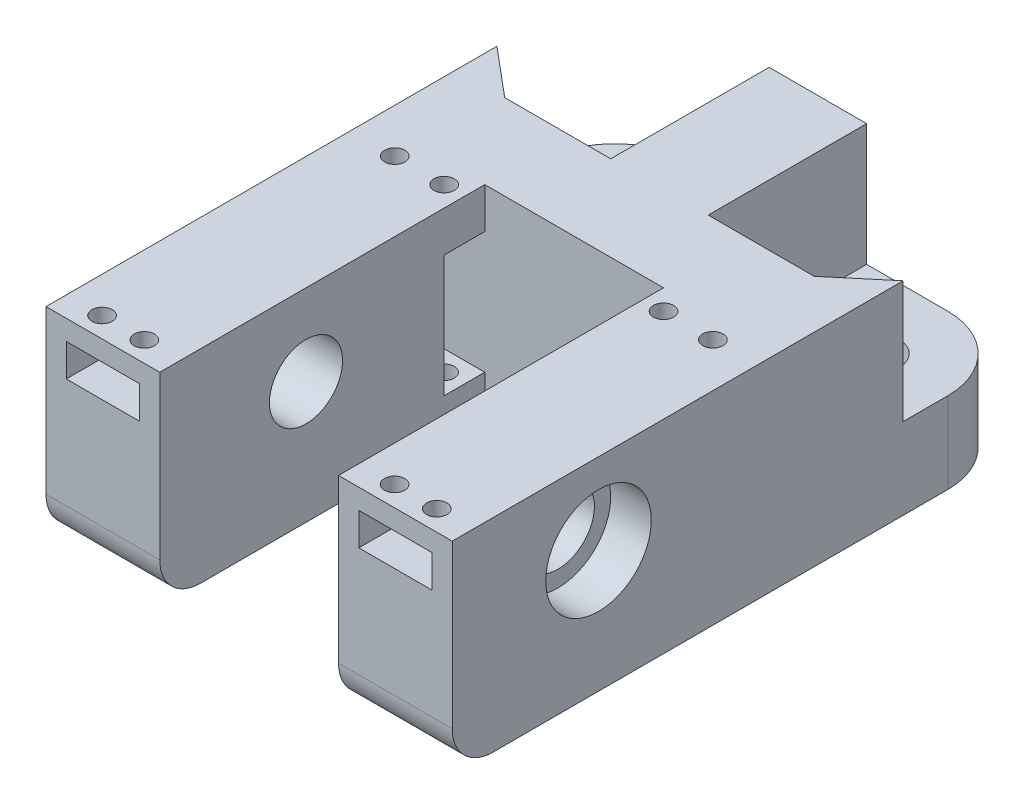
SolidWorks part; units mm, degrees
ref_plane "정면" through (0, 0, 0) normal (0, 0, 1) x (1, 0, 0)
ref_plane "윗면" through (0, 0, 0) normal (0, 1, 0) x (1, 0, 0)
ref_plane "우측면" through (0, 0, 0) normal (1, 0, 0) x (0, 0, -1)
sketch "스케치1" plane through (0, 0, 0) normal (0, 0, 1) x (1, 0, 0)
  line L1 (-25, -12.5) -> (25, -12.5)
  line L2 (-25, -12.5) -> (-25, 12.5)
  line L3 (-25, 12.5) -> (25, 12.5)
  line L4 (25, -12.5) -> (25, 12.5)
  line L5 (-25, -12.5) -> (25, 12.5) construction
  line L6 (-25, 12.5) -> (25, -12.5) construction
  point P0 (0, 0)
  dimension "D1" = 50
  dimension "D2" = 25
extrude "보스-돌출1" add sketch "스케치1" along normal blind 70
sketch "스케치2" plane through (0, 0, 70) normal (0, 0, 1) x (1, 0, 0)
  line L0 (-25, -12.5) -> (25, -12.5) construction
  line L1 (-11, -12.5) -> (11, -12.5)
  line L2 (-11, -12.5) -> (-11, 12.5)
  line L3 (-11, 12.5) -> (11, 12.5)
  line L4 (11, -12.5) -> (11, 12.5)
  line L5 (25, 12.5) -> (-25, 12.5) construction
  line L7 (0, -13.75) -> (0, 13.75) construction
  point P12 (0, -12.5)
  dimension "D1" = 22
extrude "컷-돌출1" cut sketch "스케치2" against normal blind 40
sketch "스케치3" plane through (25, 0, 0) normal (1, 0, 0) x (0, 0, -1)
  line L0 (-70, -12.5) -> (-70, 12.5) construction
  line L1 (-70, 0) -> (-16.1635, 0) construction
  line L2 (-30, -12.5) -> (-30, 12.5) construction
  line L3 (-30, -12.5) -> (-30, 12.5) construction
  line L4 (-70, 12.5) -> (0, 12.5) construction
  circle A0 centre (-52, 2.5) radius 4.5
  dimension "D1" = 9
  dimension "D2" = 22
  dimension "D3" = 10
extrude "컷-돌출2" cut sketch "스케치3" against normal blind 50
sketch "스케치4" plane through (25, 0, 0) normal (-1, 0, 0) x (0, 0, 1)
  circle A0 centre (52, 2.5) radius 6.5
  dimension "D1" = 13
extrude "컷-돌출4" cut sketch "스케치4" along normal blind 5 contours A0
sketch "스케치5" plane through (0, 12.5, 0) normal (0, 1, 0) x (1, 0, 0)
  line L0 (16, -9) -> (56.6647, -9) construction
  line L1 (16, -9) -> (16, 25.2953) construction
  line L2 (25, -70) -> (25, 0) construction
  line L3 (25, 0) -> (-25, 0) construction
  line L4 (16, 12.3557) -> (16, 0)
  line L5 (25, -9) -> (37.3557, -9)
  circle A0 centre (16, -9) radius 3
  arc A1 (25, -9) -> (16, 0) centre (16, -9) ccw
  arc A2 (37.3557, -9) -> (16, 12.3557) centre (16, -9) ccw
  dimension "D1" = 6
  dimension "D2" = 9
  dimension "D3" = 9
extrude "컷-돌출5" cut sketch "스케치5" against normal blind 29
mirror "대칭 복사2" about plane through (0, 0, 0) normal (1, 0, 0) of "컷-돌출5", "컷-돌출4"
ref_point "점1"
ref_point "점2"
ref_axis "기준축1" through (36.6861, 12.5, 9) along (-1, 0, 0)
sketch "스케치6" plane through (0, 12.5, 0) normal (0, 1, 0) x (1, 0, 0)
  line L0 (25, -70) -> (25, -9) construction
  line L2 (6, -19.5) -> (6, 5.2581)
  line L3 (25, -14.5022) -> (25, 5.2581)
  line L4 (25, 5.2581) -> (6, 5.2581)
  line L7 (19.0438, -19.5) -> (6, -19.5)
  line L9 (36.6861, -9) -> (-17.6842, -9) construction
  line L10 (19.0438, -19.5) -> (25, -14.5022)
  line L11 (16, -9) -> (6, -17.391) construction
  line L12 (-25, -14.5022) -> (-25, 5.2581)
  line L14 (0, -24.5) -> (0, 0) construction
  line L15 (-6, -19.5) -> (-6, 5.2581)
  line L16 (-19.0438, -19.5) -> (-6, -19.5)
  line L17 (-19.0438, -19.5) -> (-25, -14.5022)
  line L18 (-6, 5.2581) -> (-25, 5.2581)
  dimension "D1" = 10.5
  dimension "D2" = 10
  dimension "D3" = 40
  dimension "D4" = 10
extrude "컷-돌출6" cut sketch "스케치6" against normal blind 15 and the other way blind 5
sketch "스케치7" plane through (-11, 0, 0) normal (1, 0, 0) x (0, 0, -1)
  line L0 (-30, 0) -> (-41.4091, 0) construction
  line L1 (-30, 12.5) -> (-30, -12.5) construction
  line L2 (-30, -7.5) -> (-35, -7.5)
  line L3 (-30, 7.5) -> (-35, 7.5)
  line L4 (-30, 7.5) -> (-30, -7.5)
  line L6 (-35, 7.5) -> (-35, -7.5)
  line L7 (-30, 12.5) -> (-70, 12.5) construction
  point P12 (-35, 0)
  dimension "D1" = 5
  dimension "D2" = 5
extrude "컷-돌출7" cut sketch "스케치7" against normal blind 10
sketch "스케치8" plane through (0, -7.5, 0) normal (0, 1, 0) x (1, 0, 0)
  line L0 (-16.5374, -35) -> (-16.5374, -30) construction
  line L3 (-11, -35) -> (-11, -30) construction
  circle A0 centre (-13.5, -32.5) radius 1.25
  circle A1 centre (-19.5748, -32.5) radius 1.25
  dimension "D1" = 2.5
  dimension "D2" = 2.5
extrude "컷-돌출8" cut sketch "스케치8" against normal blind 10 and the other way blind 30 contours A1 | A0 region at (-13.5, -7.5, 32.5) region at (-19.5748, -7.5, 32.5)
sketch "스케치9" plane through (0, -12.5, 0) normal (0, -1, 0) x (1, 0, 0)
  circle A0 centre (-19.5748, 32.5) radius 2.75
  circle A1 centre (-13.5, 32.5) radius 2.75
  dimension "D1" = 5.5
extrude "컷-돌출9" cut sketch "스케치9" against normal blind 3
fillet "필렛2" radius 5 2 edges at (18, -12.5, 70) (-18, -12.5, 70)
sketch "스케치10" plane through (0, 0, 70) normal (0, 0, 1) x (1, 0, 0)
  line L0 (-18, 12.5) -> (-18, -2.0242) construction
  line L1 (-11, 12.5) -> (-25, 12.5) construction
  line L3 (-22.5, 10.0362) -> (-13.5, 10.0362)
  line L4 (-22.5, 10.0362) -> (-22.5, 6.0362)
  line L5 (-22.5, 6.0362) -> (-13.5, 6.0362)
  line L6 (-13.5, 10.0362) -> (-13.5, 6.0362)
  point P8 (-18, 10.0362)
  dimension "D1" = 9
  dimension "D2" = 4
extrude "컷-돌출10" cut sketch "스케치10" against normal blind 5
sketch "스케치12" plane through (0, 10.0362, 0) normal (0, -1, 0) x (1, 0, 0)
  line L0 (-18, 70) -> (-18, 65) construction
  line L1 (-13.5, 70) -> (-22.5, 70) construction
  line L2 (-13.5, 65) -> (-22.5, 65) construction
  line L3 (-13.5, 67.5) -> (-18, 67.5) construction
  line L4 (-13.5, 65) -> (-13.5, 70) construction
  circle A0 centre (-15.4008, 67.5) radius 1.25
  circle A1 centre (-20.5992, 67.5) radius 1.25
  dimension "D1" = 2.5
extrude "컷-돌출11" cut sketch "스케치12" against normal blind 10
mirror "대칭 복사3" about plane through (0, 0, 0) normal (1, 0, 0) of "컷-돌출10", "컷-돌출11", "컷-돌출8", "컷-돌출7", "컷-돌출9"
